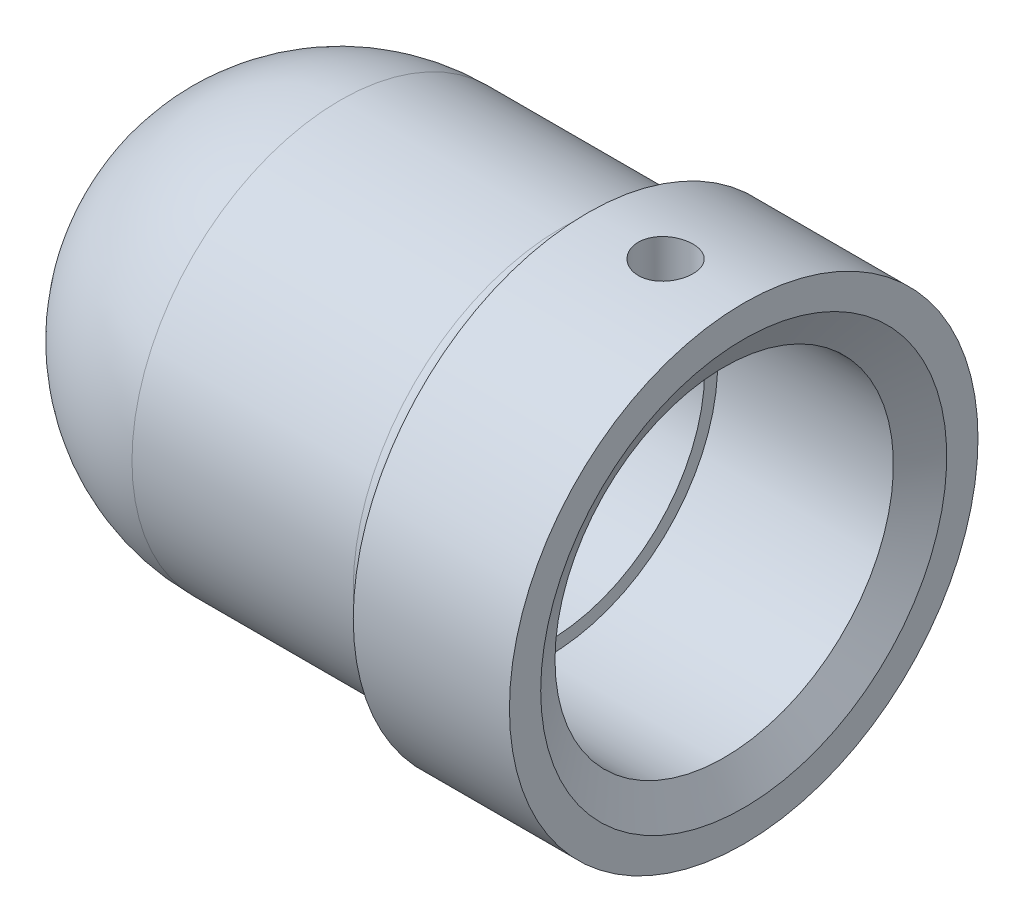
SolidWorks part; units mm, degrees
ref_plane "前视基准面" through (0, 0, 0) normal (0, 0, 1) x (1, 0, 0)
ref_plane "上视基准面" through (0, 0, 0) normal (0, 1, 0) x (1, 0, 0)
ref_plane "右视基准面" through (0, 0, 0) normal (1, 0, 0) x (0, 0, -1)
sketch "草图1" plane through (0, 0, 0) normal (0, 0, 1) x (1, 0, 0)
  line L0 (0, 13) -> (0, 18)
  line L1 (0, 18) -> (-12, 18)
  line L2 (-12, 18) -> (-12, 16)
  line L3 (-12, 16) -> (-31, 16)
  line L4 (-47, 0) -> (-43, 0)
  line L5 (-31, 12) -> (-15, 12)
  line L6 (-15, 12) -> (-15, 13)
  line L7 (-15, 13) -> (0, 13)
  arc A0 (-31, 16) -> (-47, 0) centre (-31, 0) ccw
  arc A1 (-43, 0) -> (-31, 12) centre (-31, 0) cw
  point P0 (0, 0)
  dimension "D1" = 12
  dimension "D2" = 16
  dimension "D3" = 31
  dimension "D4" = 15
  dimension "D5" = 13
  dimension "D6" = 5
  dimension "D7" = 12
revolve "旋转1" add sketch "草图1" angle 360 about L4
fillet "圆角1" radius 2 1 edges at (-12, 0, 16)
chamfer "倒角1" distance 1.5 angle 60 1 edges at (0, 0, 13) first distance on face at (0, 0, 13)
sketch "草图3" plane through (0, 0, 0) normal (0, 0, 1) x (1, 0, 0)
  line L0 (0, 18) -> (-12, 18) construction
  point P0 (-6, 18)
  point P1 (0, 0)
  point P4 (0, 0)
  dimension "D1" = 6
hole_wizard "M5 螺纹孔1" positions "3D草图1" profile "草图4" tap size "M5" standard "GB"
sketch3d "3D草图1"
  point P0 (-6, 18, 0)
  point P3 (0, 0, 0)
sketch "草图4" plane through (-6, 18, 0) normal (1, 0, 0) x (0, 0, 1)
  line L0 (0, 0) -> (0, 13.6618)
  line L1 (0, 13.6618) -> (2.1, 12.4)
  line L2 (2.1, 12.4) -> (2.1, 0)
  line L5 (2.1, 0) -> (0, 0)
  line L10 (0, 13.6618) -> (-2.1, 12.4) construction
  line L11 (0, -6.35) -> (0, 107.95) construction
  dimension "螺纹孔钻头直径" = 4.2
  dimension "螺纹孔钻头深度" = 12.4
  dimension "导头角度" = 118
cosmetic thread "孔螺蚊线1" parameters "D1"=10, "D2"=5
